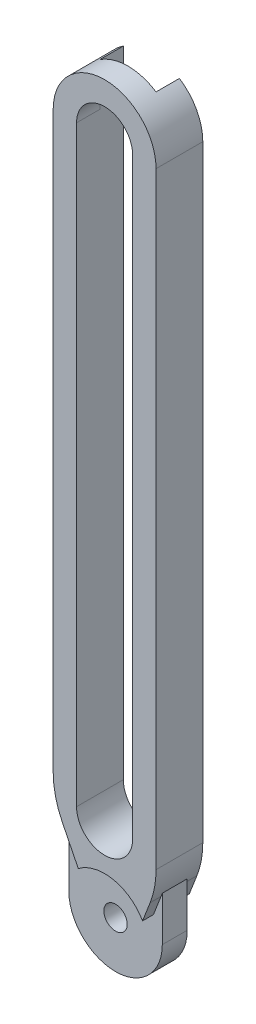
SolidWorks part; units mm, degrees
ref_plane "Piano frontale" through (0, 0, 0) normal (0, 0, 1) x (1, 0, 0)
ref_plane "Piano superiore" through (0, 0, 0) normal (0, 1, 0) x (1, 0, 0)
ref_plane "Piano destro" through (0, 0, 0) normal (1, 0, 0) x (0, 0, -1)
sketch "Schizzo1" plane through (0, 0, 0) normal (0, 0, 1) x (1, 0, 0)
  line L0 (0, -86.6264) -> (0, 113.3736) construction
  line L1 (-16.5, -86.6264) -> (-16.5, 113.3736)
  line L2 (16.5, -86.6264) -> (16.5, 113.3736)
  arc A0 (-16.5, -86.6264) -> (16.5, -86.6264) centre (0, -86.6264) ccw
  arc A1 (16.5, 113.3736) -> (-16.5, 113.3736) centre (0, 113.3736) ccw
  point P2 (0, 13.3736)
  point P8 (0, 83.3736)
  point P9 (0, 113.7918)
  dimension "D1" = 33
  dimension "D2" = 200
extrude "Estrusione-Estrusione1" add sketch "Schizzo1" along normal mid plane 15
sketch "Schizzo2" plane through (0, 0, 0) normal (0, 0, 1) x (1, 0, 0)
  line L0 (0, -88.7045) -> (0, -104.7045) construction
  line L1 (15, -88.7045) -> (15, -104.7045)
  line L2 (-15, -88.7045) -> (-15, -104.7045)
  line L3 (16.5, -86.6264) -> (-16.5, -86.6264) construction
  arc A0 (15, -88.7045) -> (-15, -88.7045) centre (0, -88.7045) ccw
  arc A1 (-15, -104.7045) -> (15, -104.7045) centre (0, -104.7045) ccw
  point P3 (0, -96.7045)
  dimension "D1" = 15
  dimension "D2" = 16
extrude "Estrusione-Estrusione2" add sketch "Schizzo2" along normal mid plane 8
sketch "Schizzo3" plane through (0, 0, 4) normal (0, 0, 1) x (1, 0, 0)
  line L0 (0, -104.7045) -> (15, -104.7045) construction
  line L1 (-8.4489, -93.5413) -> (-16.5, -77.3405)
  line L2 (-16.5, 113.3736) -> (-16.5, -86.6264) construction
  line L3 (-16.5, -77.3405) -> (-21.7067, -99.1177)
  line L4 (-21.7067, -99.1177) -> (-12.1597, -111.6429)
  line L5 (12.1644, -97.7744) -> (16.5, -86.6264)
  line L6 (16.5, -86.6264) -> (21.2626, -91.5332)
  line L7 (21.2626, -91.5332) -> (13.9976, -104.4458)
  arc A0 (-12.1597, -111.6429) -> (13.9976, -104.4458) centre (0, -104.7045) ccw
  arc A1 (12.1644, -97.7744) -> (-8.4489, -93.5413) centre (0, -104.7045) ccw
  arc A2 (-15, -93.5003) -> (15, -93.5003) centre (0, -86.6264) ccw construction
  point P12 (11.5464, -96.7869)
  dimension "D1" = 28
extrude "Taglio-Estrusione1" cut sketch "Schizzo3" along normal blind 4
mirror "Specchia1" about plane through (0, 0, 0) normal (0, 0, 1) of "Taglio-Estrusione1"
sketch "Schizzo4" plane through (0, 0, 4) normal (0, 0, 1) x (1, 0, 0)
  line L0 (-15, -93.5003) -> (-15, -80.3588)
  line L1 (-8.4489, -93.5413) -> (-16.5, -77.3405) construction
  line L2 (-15, -80.3588) -> (-16.5, -77.3405)
  line L3 (-16.5, -77.3405) -> (-16.5, -93.5003)
  line L4 (-16.5, -93.5003) -> (-15, -93.5003)
  line L5 (15, -93.5003) -> (15, -90.4833)
  line L6 (12.1644, -97.7744) -> (16.5, -86.6264) construction
  line L7 (15, -90.4833) -> (16.5, -86.6264)
  line L8 (16.5, -86.6264) -> (16.5, -93.5003)
  line L9 (16.5, -93.5003) -> (15, -93.5003)
extrude "Taglio-Estrusione2" cut sketch "Schizzo4" against normal blind 8
fillet "Raccordo1" radius 28 2 edges at (-16.5, -77.3405, 0) (16.5, -86.6264, 0)
sketch "Schizzo9" plane through (0, 0, 4) normal (0, 0, 1) x (1, 0, 0)
  line L0 (0, -104.7045) -> (15, -104.7045) construction
hole_wizard "Foro per Vite M6.5-1" positions "Schizzo3D4" profile "Schizzo10" hole size "M6.5" standard "ISO"
sketch3d "Schizzo3D4"
  point P0 (0, -104.7045, 4)
sketch "Schizzo10" plane through (0, -104.7045, 4) normal (1, 0, 0) x (0, -1, 0)
  line L0 (0, 0) -> (0, 10.2532)
  line L1 (0, 10.2532) -> (3.75, 8)
  line L2 (3.75, 8) -> (3.75, 0)
  line L5 (3.75, 0) -> (0, 0)
  line L10 (0, 10.2532) -> (-3.75, 8) construction
  line L11 (0, -6.35) -> (0, 107.95) construction
  dimension "Hole Dia." = 7.5
  dimension "Hole Depth" = 8
  dimension "Drill Angle" = 118
sketch "Schizzo11" plane through (0, 0, 7.5) normal (0, 0, 1) x (1, 0, 0)
  line L0 (0, 113.3736) -> (0, -76.6264) construction
  line L1 (9, 113.3736) -> (9, -76.6264)
  line L2 (-9, 113.3736) -> (-9, -76.6264)
  arc A0 (9, 113.3736) -> (-9, 113.3736) centre (0, 113.3736) ccw
  arc A1 (-9, -76.6264) -> (9, -76.6264) centre (0, -76.6264) ccw
  point P4 (0, 18.3736)
  point P9 (0, -75.5802)
  dimension "D1" = 9
  dimension "D2" = 190
extrude "Taglio-Estrusione3" cut sketch "Schizzo11" against normal through all
sketch "Schizzo13" plane through (0, 0, -7.5) normal (0, 0, -1) x (-1, 0, 0)
  line L0 (0, 113.3736) -> (0, 158.8684) construction
  line L1 (-9, 113.3736) -> (-9, 158.8684)
  line L2 (9, 113.3736) -> (9, 158.8684)
  line L3 (-9, -76.6264) -> (-9, 113.3736) construction
  arc A0 (-9, 113.3736) -> (9, 113.3736) centre (0, 113.3736) ccw
  arc A1 (9, 158.8684) -> (-9, 158.8684) centre (0, 158.8684) ccw
  point P4 (0, 136.121)
extrude "Taglio-Estrusione4" cut sketch "Schizzo13" against normal blind 7.5
equation "\"80ù\"=90"
